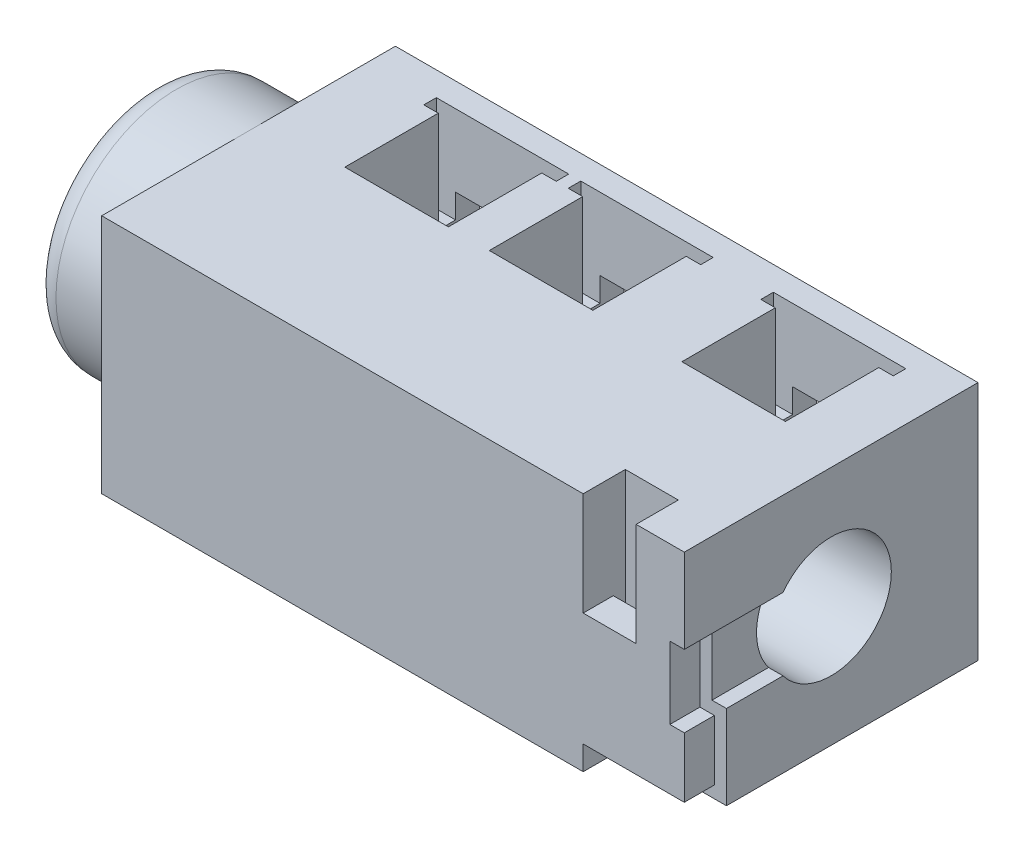
SolidWorks part; units mm, degrees
ref_plane "前视基准面" through (0, 0, 0) normal (0, 0, 1) x (1, 0, 0)
ref_plane "上视基准面" through (0, 0, 0) normal (0, 1, 0) x (1, 0, 0)
ref_plane "右视基准面" through (0, 0, 0) normal (1, 0, 0) x (0, 0, -1)
sketch "草图1" plane through (0, 0, 0) normal (0, 1, 0) x (1, 0, 0)
  line L0 (-2.2848, 0) -> (10.6662, 0) construction
  line L2 (12.1, -3.05) -> (0, -3.05)
  line L3 (12.1, -3.05) -> (12.1, 3.05)
  line L4 (12.1, 3.05) -> (0, 3.05)
  line L5 (0, -3.05) -> (0, 3.05)
  line L6 (12.1, -3.05) -> (0, 3.05) construction
  line L7 (12.1, 3.05) -> (0, -3.05) construction
  point P1 (6.05, 0)
  dimension "D1" = 6.1
  dimension "D2" = 12.1
extrude "凸台-拉伸1" add sketch "草图1" along normal blind 5
sketch "草图3" plane through (0, 0, 0) normal (-1, 0, 0) x (0, 0, 1)
  line L0 (0, 5) -> (0, 0) construction
  line L1 (-3.05, 5) -> (3.05, 5) construction
  circle A0 centre (0, 2.5) radius 2.5
  dimension "D1" = 5
extrude "凸台-拉伸2" add sketch "草图3" along normal blind 2
sketch "草图4" plane through (0, 0, 0) normal (0, -1, 0) x (1, 0, 0)
  line L0 (0, 0) -> (12.1, 0) construction
  line L1 (12.1, 3.05) -> (12.1, -3.05) construction
  line L3 (0, 0) -> (0, 3.05) construction
  circle A0 centre (1.6, 0) radius 0.75
  circle A1 centre (8.6, 0) radius 0.75
  dimension "D1" = 1.5
  dimension "D2" = 1.6
  dimension "D3" = 7
extrude "凸台-拉伸3" add sketch "草图4" along normal blind 1
fillet "圆角1" radius 0.5 2 edges at (8.6, -1, -0.75) (1.6, -1, -0.75)
sketch "草图6" plane through (0, 0, -3.05) normal (0, 0, -1) x (-1, 0, 0)
  line L0 (-1.75, 0) -> (-1.75, 3.5)
  line L1 (-12.1, 0) -> (0, 0) construction
  line L2 (-1.75, 3.5) -> (-2.6153, 3.5)
  line L3 (-2.6153, 3.5) -> (-2.6153, 0.5)
  line L4 (-2.6153, 0.5) -> (-3.7, 0.5)
  line L6 (-3.7, 0.5) -> (-3.7, 0)
  line L7 (-3.7, 0) -> (-1.75, 0)
  line L8 (-12.1, 5) -> (0, 5) construction
  line L10 (-6.7, 0.5) -> (-6.7, 0)
  line L11 (-4.75, 0) -> (-4.75, 3.5)
  line L12 (-4.75, 3.5) -> (-5.6153, 3.5)
  line L13 (-5.6153, 0.5) -> (-6.7, 0.5)
  line L14 (-5.6153, 3.5) -> (-5.6153, 0.5)
  line L15 (-6.7, 0) -> (-4.75, 0)
  line L16 (-8.75, 3.5) -> (-9.6153, 3.5)
  line L17 (-9.6153, 3.5) -> (-9.6153, 0.5)
  line L18 (-10.7, 0) -> (-8.75, 0)
  line L19 (-8.75, 0) -> (-8.75, 3.5)
  line L20 (-9.6153, 0.5) -> (-10.7, 0.5)
  line L21 (-10.7, 0.5) -> (-10.7, 0)
  line L22 (-3.7, 4.05) -> (-3.7, -2.5) construction
  dimension "D1" = 0.5
  dimension "D2" = 1.5
extrude "切除-拉伸2" cut sketch "草图6" against normal up to surface (0.875 mm away)
sketch "草图8" plane through (0, 5, 0) normal (0, 1, 0) x (1, 0, 0)
  line L0 (12.1, 3.05) -> (0, 3.05) construction
  line L1 (8.35, 2.55) -> (11.1, 2.55)
  line L2 (8.65, 2.2902) -> (8.65, 0.35)
  line L3 (8.65, 0.35) -> (10.8, 0.35)
  line L7 (9.725, 0.35) -> (9.725, 2.5501) construction
  line L10 (8.65, 2.2902) -> (8.35, 2.2902)
  line L11 (8.35, 2.55) -> (8.35, 2.2902)
  line L12 (11.1, 2.55) -> (11.1, 2.2902)
  line L13 (10.8, 2.2902) -> (11.1, 2.2902)
  line L14 (10.8, 2.2902) -> (10.8, 0.35)
  line L15 (4.35, 2.55) -> (7.1, 2.55)
  line L16 (7.1, 2.55) -> (7.1, 2.2902)
  line L17 (6.8, 2.2902) -> (7.1, 2.2902)
  line L18 (6.8, 2.2902) -> (6.8, 0.35)
  line L19 (4.65, 0.35) -> (6.8, 0.35)
  line L20 (4.65, 2.2902) -> (4.65, 0.35)
  line L21 (4.65, 2.2902) -> (4.35, 2.2902)
  line L22 (4.35, 2.55) -> (4.35, 2.2902)
  line L23 (1.35, 2.55) -> (4.1, 2.55)
  line L24 (4.1, 2.55) -> (4.1, 2.2902)
  line L25 (3.8, 2.2902) -> (4.1, 2.2902)
  line L26 (3.8, 2.2902) -> (3.8, 0.35)
  line L27 (1.65, 0.35) -> (3.8, 0.35)
  line L28 (1.65, 2.2902) -> (1.65, 0.35)
  line L29 (1.65, 2.2902) -> (1.35, 2.2902)
  line L30 (1.35, 2.55) -> (1.35, 2.2902)
  line L31 (8.75, 0.8567) -> (8.75, 0.1067) construction
  point P7 (9.725, 2.55)
  dimension "D1" = 0.5
  dimension "D2" = 2.2
  dimension "D3" = 0.1
  dimension "D4" = 0.3
  dimension "D5" = 2
  dimension "D6" = 2
extrude "切除-拉伸4" cut sketch "草图8" against normal blind 2
ref_axis "基准轴1" through (-2, 2.5, 0) along (1, 0, 0)
ref_plane "基准面1" through (0, 2.5, 0) normal (0, 1, 0) x (1, 0, 0)
sketch "草图9" plane through (0, 2.5, 0) normal (0, 1, 0) x (1, 0, 0)
  line L0 (-0.9078, 0) -> (1.0705, 0) construction
  line L1 (-2, 0) -> (-2, 1.8)
  line L2 (-2, 1.8) -> (5, 1.8)
  line L3 (5, 1.8) -> (5, 1.5)
  line L4 (5, 1.5) -> (8, 1.5)
  line L5 (8, 1.5) -> (8, 1.25)
  line L6 (8, 1.25) -> (12.1, 1.25)
  line L7 (12.1, 1.25) -> (12.1, 0)
  line L8 (12.1, 0) -> (-2, 0)
  line L9 (12.1, -3.05) -> (12.1, 3.05) construction
  line L10 (-2, 2.5) -> (-2, -2.5) construction
  line L11 (-2, 0) -> (0, 0) construction
  dimension "D1" = 1.8
  dimension "D2" = 1.5
  dimension "D3" = 1.25
  dimension "D4" = 3
  dimension "D5" = 7
revolve "切除-旋转1" cut sketch "草图9" angle 360 about L0
fillet "圆角2" radius 0.5 1 edges at (-2, 2.5, 2.5)
sketch "草图10" plane through (0, 0, 3.05) normal (0, 0, 1) x (1, 0, 0)
  line L0 (0, 5) -> (12.1, 5) construction
  line L1 (10, 5) -> (11.1, 5)
  line L2 (10, 5) -> (10, 2.8539)
  line L3 (10, 2.8539) -> (11.1, 2.8539)
  line L4 (11.1, 5) -> (11.1, 2.8539)
  line L5 (0, 0) -> (12.1, 0) construction
  line L6 (10, 0) -> (12.1, 0)
  line L7 (10, 0) -> (10, 0.5)
  line L8 (10, 0.5) -> (12.1, 0.5)
  line L9 (12.1, 0) -> (12.1, 0.5)
  line L10 (12.1, 5) -> (12.1, 0) construction
  line L12 (12.1, 1.75) -> (11.8, 1.75)
  line L13 (12.1, 1.75) -> (12.1, 3.25)
  line L14 (12.1, 3.25) -> (11.8, 3.25)
  line L15 (11.8, 1.75) -> (11.8, 3.25)
  point P18 (12.1, 2.5)
  point P19 (11.8, 2.5)
  dimension "D1" = 1
  dimension "D2" = 1.1
  dimension "D3" = 0.3
  dimension "D4" = 2.1
  dimension "D5" = 0.5
  dimension "D6" = 1.5
extrude "切除-拉伸5" cut sketch "草图10" against normal up to surface (0.875 mm away)
sketch "草图11" plane through (0, 0, 0) normal (0, -1, 0) x (1, 0, 0)
  line L0 (12.1, 2.175) -> (12.1, 3.05) construction
  line L1 (10, 2.175) -> (12.1, 2.175)
  line L2 (10, 2.175) -> (10, 2.425)
  line L3 (10, 2.425) -> (12.1, 2.425)
  line L4 (12.1, 2.175) -> (12.1, 2.425)
extrude "切除-拉伸6" cut sketch "草图11" against normal up to surface (3.25 mm away) up to face at (11.95, 3.25, 2.6125)
sketch "草图12" plane through (0, 0, 3.05) normal (0, 0, 1) x (1, 0, 0)
  line L1 (11.8, 1.75) -> (12.1, 1.75)
  line L2 (11.8, 1.75) -> (11.8, 3.25)
  line L3 (11.8, 3.25) -> (12.1, 3.25)
  line L4 (12.1, 1.75) -> (12.1, 3.25)
extrude "切除-拉伸7" cut sketch "草图12" against normal blind 3
